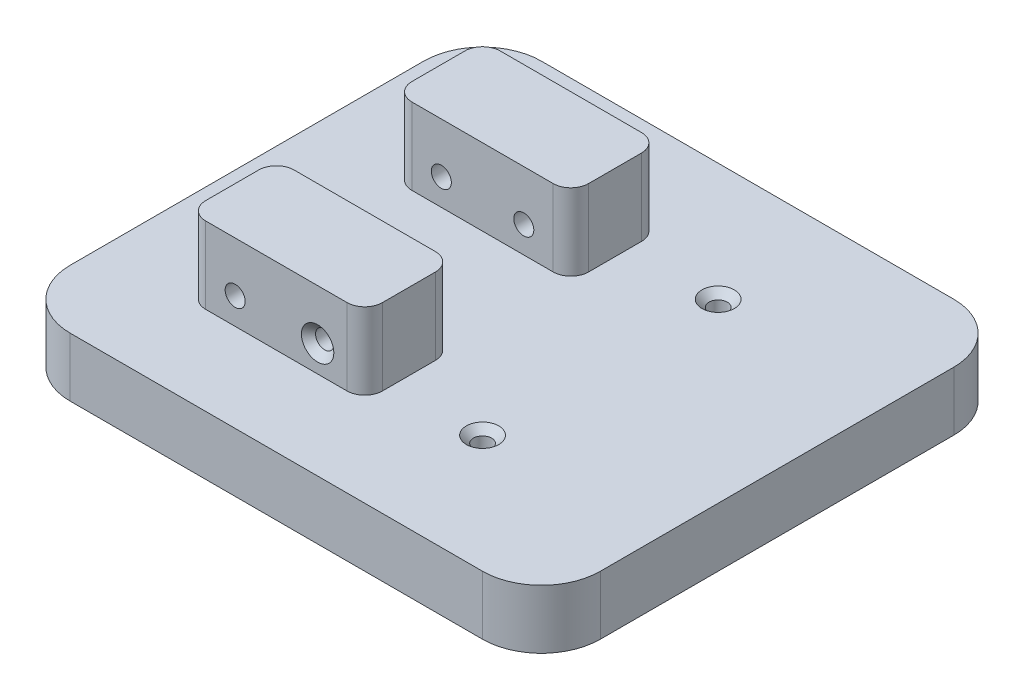
SolidWorks part; units mm, degrees
ref_plane "Piano frontale" through (0, 0, 0) normal (0, 0, 1) x (1, 0, 0)
ref_plane "Piano superiore" through (0, 0, 0) normal (0, 1, 0) x (1, 0, 0)
ref_plane "Piano destro" through (0, 0, 0) normal (1, 0, 0) x (0, 0, -1)
sketch "Schizzo1" plane through (0, 0, 0) normal (0, 1, 0) x (1, 0, 0)
  line L0 (-47.6, 35.6) -> (-47.6, -44.4)
  line L1 (-47.6, 35.6) -> (42.4, 35.6)
  line L2 (42.4, 35.6) -> (42.4, -44.4)
  line L3 (42.4, -44.4) -> (-47.6, -44.4)
  dimension "D1" = 80
  dimension "D2" = 90
extrude "Estrusione-Estrusione1" add sketch "Schizzo1" along normal blind 10
fillet "Raccordo1" radius 10 4 edges at (-47.6, 5, -35.6) (42.4, 5, -35.6) (-47.6, 5, 44.4) (42.4, 5, 44.4)
sketch "Schizzo2" plane through (0, 10, 0) normal (0, 1, 0) x (1, 0, 0)
  line L0 (12.4, -44.4) -> (12.4, 35.6) construction
  line L1 (-37.6, -44.4) -> (32.4, -44.4) construction
  line L2 (32.4, 35.6) -> (-37.6, 35.6) construction
  line L3 (-47.6, 25.6) -> (-47.6, -34.4) construction
  line L4 (12.4, -4.4) -> (-47.6, -4.4) construction
  line L5 (12.4, 15.6) -> (-47.6, 15.6) construction
  line L7 (12.4, -24.4) -> (-47.6, -24.4) construction
  dimension "D1" = 60
  dimension "D2" = 20
  dimension "D3" = 20
hole_wizard "Foro svasato per Vite M2.5-1" positions "Schizzo3D1" profile "Schizzo3" countersink size "M2.5" standard "IS" end condition through all
sketch3d "Schizzo3D1"
  point P0 (12.4, 10, -15.6)
  point P3 (12.4, 10, 24.4)
sketch "Schizzo3" plane through (12.4, 10, -15.6) normal (1, 0, 0) x (0, 0, 1)
  line L0 (0, 0) -> (0, 10)
  line L1 (0, 10) -> (1.55, 10)
  line L2 (1.55, 10) -> (1.55, 1.2)
  line L3 (1.55, 1.2) -> (2.75, 0)
  line L5 (2.75, 0) -> (0, 0)
  line L6 (-1.55, 1.2) -> (-2.75, 0) construction
  line L11 (0, -6.35) -> (0, 107.95) construction
  dimension "Thru Hole Dia." = 3.1
  dimension "Thru Hole Depth" = 10
  dimension "Near C'Sink Dia." = 5.5
  dimension "Near C'Sink Angle" = 90
sketch "Schizzo4" plane through (0, 10, 0) normal (0, 1, 0) x (1, 0, 0)
  line L0 (-32.6, 20.6) -> (-32.6, 5.6)
  line L1 (-32.6, 5.6) -> (-2.6, 5.6)
  line L2 (-2.6, 5.6) -> (-2.6, 20.6)
  line L3 (-2.6, 20.6) -> (-32.6, 20.6)
  line L4 (-2.6, -14.4) -> (-2.6, -29.4)
  line L5 (-2.6, -29.4) -> (-32.6, -29.4)
  line L6 (-32.6, -29.4) -> (-32.6, -14.4)
  line L7 (-32.6, -14.4) -> (-2.6, -14.4)
  line L8 (-47.6, -4.4) -> (42.4, -4.4) construction
  line L10 (-47.6, 25.6) -> (-47.6, -34.4) construction
  line L11 (42.4, -34.4) -> (42.4, 25.6) construction
  dimension "D1" = 15
  dimension "D2" = 15
  dimension "D3" = 10
  dimension "D4" = 10
  dimension "D5" = 15
  dimension "D6" = 30
  dimension "D7" = 30
extrude "Estrusione-Estrusione2" add sketch "Schizzo4" along normal blind 13
sketch "Schizzo5" plane through (0, 0, -20.6) normal (0, 0, -1) x (-1, 0, 0)
  line L0 (32.6, 14.5) -> (2.6, 14.5) construction
  line L1 (2.6, 23) -> (2.6, 10) construction
  line L2 (10.6, 10) -> (10.6, 23) construction
  line L3 (-12.4, 10) -> (47.6, 10) construction
  line L4 (2.6, 23) -> (32.6, 23) construction
  line L6 (24.6, 10) -> (24.6, 23) construction
  line L7 (32.6, 23) -> (32.6, 10) construction
  circle A0 centre (10.6, 14.5) radius 1.7
  circle A1 centre (24.6, 14.5) radius 1.7
  dimension "D4" = 3.4
  dimension "D5" = 3.4
  dimension "D1" = 4.5
  dimension "D2" = 8
  dimension "D3" = 8
sketch "Schizzo6" plane through (0, 0, 29.4) normal (0, 0, 1) x (1, 0, 0)
  line L0 (-32.6, 14.5) -> (-2.6, 14.5) construction
  line L1 (-37.6, 10) -> (32.4, 10) construction
  line L2 (-10.6, 23) -> (-10.6, 10) construction
  line L4 (-24.6, 23) -> (-24.6, 10) construction
  circle A0 centre (-24.6, 14.5) radius 1.7
  dimension "D2" = 3.4
  dimension "D1" = 4.5
hole_wizard "Foro svasato per Vite M2.5-2" positions "Schizzo3D4" profile "Schizzo10" countersink size "M2.5" standard "IS"
sketch3d "Schizzo3D4"
  line L0 (-32.6, 14.5, 29.4) -> (-2.6, 14.5, 29.4) construction
  line L1 (-10.6, 23, 29.4) -> (-10.6, 10, 29.4) construction
  point P0 (-10.6, 14.5, 29.4)
sketch "Schizzo10" plane through (-10.6, 14.5, 29.4) normal (1, 0, 0) x (0, -1, 0)
  line L0 (0, 0) -> (0, 15.9313)
  line L1 (0, 15.9313) -> (1.55, 15)
  line L2 (1.55, 15) -> (1.55, 1.2)
  line L3 (1.55, 1.2) -> (2.75, 0)
  line L5 (2.75, 0) -> (0, 0)
  line L6 (-1.55, 1.2) -> (-2.75, 0) construction
  line L10 (0, 15.9313) -> (-1.55, 15) construction
  line L11 (0, -6.35) -> (0, 107.95) construction
  dimension "Hole Dia." = 3.1
  dimension "Hole Depth" = 15
  dimension "Near C'Sink Dia." = 5.5
  dimension "Near C'Sink Angle" = 90
  dimension "Drill Angle" = 118
fillet "Raccordo2" radius 3 8 edges at (-2.6, 16.5, -20.6) (-2.6, 16.5, -5.6) (-32.6, 16.5, -20.6) (-32.6, 16.5, -5.6) (-2.6, 16.5, 29.4) (-2.6, 16.5, 14.4) (-32.6, 16.5, 14.4) (-32.6, 16.5, 29.4)
extrude "Taglio-Estrusione4" cut sketch "Schizzo5" against normal blind 15
extrude "Taglio-Estrusione5" cut sketch "Schizzo6" against normal blind 15
